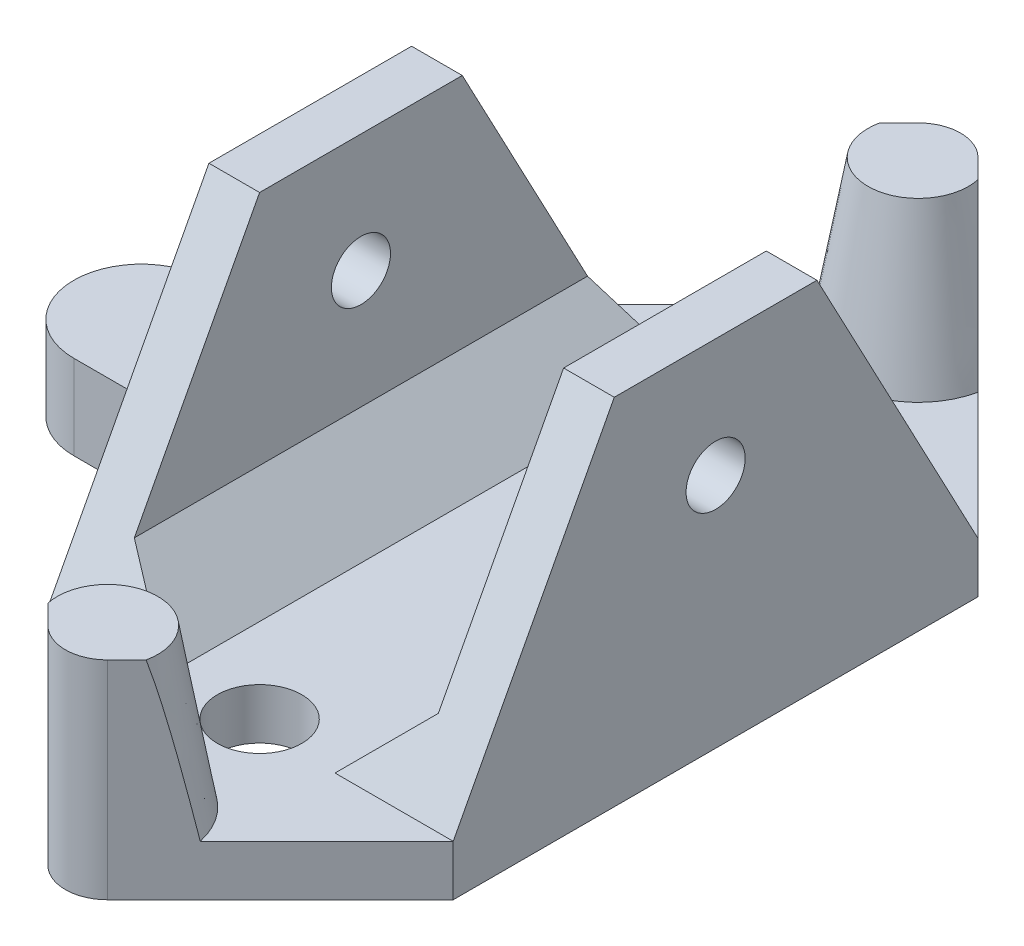
SolidWorks part; units mm, degrees
ref_plane "Plano frontal" through (0, 0, 0) normal (0, 0, 1) x (1, 0, 0)
ref_plane "Plano superior" through (0, 0, 0) normal (0, 1, 0) x (1, 0, 0)
ref_plane "Plano direito" through (0, 0, 0) normal (1, 0, 0) x (0, 0, -1)
sketch "Esboço1" plane through (0, 0, 0) normal (0, 1, 0) x (1, 0, 0)
  line L0 (0, -15) -> (0, 15) construction
  line L1 (-13, -26.5) -> (13, -26.5)
  line L2 (-13, -26.5) -> (-13, -6)
  line L3 (-13, 26.5) -> (13, 26.5)
  line L4 (13, -26.5) -> (13, -6)
  line L5 (-13, -26.5) -> (13, 26.5) construction
  line L6 (-13, 26.5) -> (13, -26.5) construction
  line L7 (0, 24) -> (0, 26.5)
  line L8 (0, 24) -> (-2.5, 24)
  line L9 (0, 24) -> (-2.5, 26.5) construction
  line L10 (0, 24) -> (2.5, 26.5) construction
  line L11 (-1.7678, 25.7678) -> (-13, 14.5355)
  line L12 (1.7678, 25.7678) -> (13, 14.5355)
  line L13 (-7.3839, 0) -> (7.3839, 0) construction
  line L14 (-9, -6) -> (-9, 6)
  line L15 (1.7678, -25.7678) -> (13, -14.5355)
  line L16 (-12, -6) -> (-12, 6)
  line L17 (13, 6) -> (9, 6)
  line L18 (9, -6) -> (9, 6)
  line L19 (-13, 6) -> (-9, 6)
  line L20 (13, -6) -> (9, -6)
  line L21 (-13, -6) -> (-9, -6)
  line L22 (-1.7678, -25.7678) -> (-13, -14.5355)
  line L23 (12, 6) -> (12, -6)
  line L24 (13, 6) -> (13, 26.5)
  line L25 (-13, 6) -> (-13, 26.5)
  circle A0 centre (0, 15) radius 2.5
  circle A1 centre (0, -15) radius 2.5
  circle A2 centre (0, 24) radius 2.5
  circle A3 centre (0, -24) radius 2.5
  point P0 (0, 0)
  point P9 (0, 0)
  point P24 (0, 0)
  point P35 (-9, 0)
  dimension "D4" = 5
  dimension "D5" = 5
  dimension "D6" = 5
  dimension "D1" = 26
  dimension "D2" = 53
  dimension "D3" = 30
  dimension "D7" = 2.5
  dimension "D8" = 12
  dimension "D9" = 4
  dimension "D10" = 3
  dimension "D11" = 3
extrude "Ressalto-extrusão1" add sketch "Esboço1" along normal blind 5 contours L22 A3 L15 L4 L20 L18 L17 L12 A2 L11 L2 L19 L14 L21 A1 A0 region at (0, 0, 0)
extrude "Ressalto-extrusão2" add sketch "Esboço1<3>" along normal blind 12.3 contours A3 | A2 L7 L8 | L7 A2 L8 region at (0, 0, 24) region at (-1.061, 0, -25.061) region at (0.3537, 0, -23.6463)
sketch "Esboço1<3>" plane through (0, 0, 0) normal (0, 1, 0) x (1, 0, 0) same geometry as "Esboço1"
extrude "Ressalto-extrusão3" add sketch "Esboço1<4>" along normal blind 21 contours L20 L4 L17 L18 | L2 L21 L14 L19 region at (-10.5, 0, 0) region at (10.5, 0, 0)
sketch "Esboço1<4>" plane through (0, 0, 0) normal (0, 1, 0) x (1, 0, 0) same geometry as "Esboço1"
sketch "Esboço2" plane through (13, 0, 0) normal (1, 0, 0) x (0, 0, -1)
  line L0 (0, 0) -> (0, 14)
  circle A0 centre (0, 14) radius 1.75
  dimension "D2" = 3.5
  dimension "D1" = 14
extrude "Corte-extrusão1" cut sketch "Esboço2" against normal through all contours A0 region at (13, 12.7976, -1.2024)
ref_plane "Plano1" through (0, 0, 0) normal (1, 0, 0) x (0, 0, -1)
sketch "Esboço12" plane through (-13, 0, 0) normal (-1, 0, 0) x (0, 0, 1)
  line L1 (6, 5) -> (21, 5)
  line L2 (6, 5) -> (6, 0)
  line L3 (6, 0) -> (21, 0)
  line L4 (21, 5) -> (21, 0)
  line L5 (-6, 5) -> (-21, 5)
  line L6 (-6, 5) -> (-6, 0)
  line L7 (-6, 0) -> (-21, 0)
  line L8 (-21, 5) -> (-21, 0)
  dimension "D1" = 15
  dimension "D2" = 15
extrude "Corte-extrusão4" cut sketch "Esboço12" against normal blind 1
mirror "Espelhar2" about plane through (0, 0, 0) normal (1, 0, 0) of "Corte-extrusão4"
sketch "Esboço19" plane through (0, 5, 0) normal (0, 1, 0) x (1, 0, 0)
  line L10 (-9, 6) -> (-9, -6)
  line L11 (12, 6) -> (12, 15.5355)
  line L12 (-12, -15.5355) -> (-1.7678, -25.7678)
  line L13 (1.7678, -25.7678) -> (12, -15.5355)
  line L14 (12, 6) -> (12, 15.5355)
  line L15 (9, -6) -> (9, 6)
  line L16 (-12, 15.5355) -> (-12, 9)
  line L17 (12, 15.5355) -> (1.7678, 25.7678)
  line L18 (-1.7678, 25.7678) -> (-12, 15.5355)
  line L19 (-12, 15.5355) -> (-12, 9)
  line L20 (-9, 6) -> (-9, -6)
  line L21 (-12, 9) -> (-12, 6)
  line L22 (-12, -15.5355) -> (-1.7678, -25.7678)
  line L23 (1.7678, -25.7678) -> (12, -15.5355)
  line L24 (-12, 9) -> (-12, 6)
  line L25 (9, -6) -> (9, 6)
  line L26 (-12, 6) -> (-9, 6)
  line L27 (12, 15.5355) -> (1.7678, 25.7678)
  line L28 (-1.7678, 25.7678) -> (-12, 15.5355)
  line L29 (-12, 6) -> (-9, 6)
  line L36 (-9, -6) -> (-12, -6)
  line L37 (-9, -6) -> (-12, -6)
  line L38 (-12, -6) -> (-12, -9)
  line L39 (-12, -6) -> (-12, -9)
  line L40 (-12, -9) -> (-12, -15.5355)
  line L41 (-12, -9) -> (-12, -15.5355)
  line L42 (12, -15.5355) -> (12, -6)
  line L43 (12, -15.5355) -> (12, -6)
  line L44 (12, -6) -> (9, -6)
  line L45 (12, -6) -> (9, -6)
  line L46 (9, 6) -> (12, 6)
  line L47 (9, 6) -> (12, 6)
  arc A2 (1.7678, -25.7678) -> (-1.7678, -25.7678) centre (0, -24) ccw
  arc A3 (-1.7678, 25.7678) -> (1.7678, 25.7678) centre (0, 24) ccw
  arc A4 (1.7678, -25.7678) -> (-1.7678, -25.7678) centre (0, -24) ccw
  arc A5 (-1.7678, 25.7678) -> (1.7678, 25.7678) centre (0, 24) ccw
  dimension "D1" = 0
extrude "Corte-extrusão5" cut sketch "Esboço19" against normal blind 2
chamfer "Chanfro3" distance 12 angle 10 1 edges at (0, 3, -21.5) first distance on face at (0, 1.5, -24.8839)
chamfer "Chanfro4" distance 12 angle 10 1 edges at (0, 3, 21.5) first distance on face at (0, 1.5, 24.8839)
sketch "Esboço20" plane through (12, 0, 0) normal (1, 0, 0) x (0, 0, -1)
  line L0 (-15.5355, 3) -> (-6, 3)
  line L1 (-6, 3) -> (-6, 21)
  line L2 (-6, 21) -> (-15.5355, 3)
  line L3 (0, 21) -> (0, 14) construction
  line L4 (6, 21) -> (-6, 21) construction
  line L5 (15.5355, 3) -> (6, 3)
  line L6 (6, 3) -> (6, 21)
  line L7 (6, 21) -> (15.5355, 3)
extrude "Ressalto-extrusão4" add sketch "Esboço20" against normal blind 3
mirror "Espelhar3" about plane through (0, 0, 0) normal (1, 0, 0) of "Ressalto-extrusão4"
chamfer "Chanfro6" distance 4 angle 45 2 edges at (9, 3, 0) (-9, 3, 0)
sketch "Esboço21" plane through (0, 0, 0) normal (0, -1, 0) x (-1, 0, 0)
  line L0 (12, 0) -> (26, 0) construction
  line L1 (12, -15.5355) -> (12, 15.5355) construction
  line L2 (26, 4) -> (26, -4)
  line L4 (26, -4) -> (12, -4)
  line L5 (26, -4) -> (26, 4)
  line L6 (26, 4) -> (12, 4)
  line L7 (12, -4) -> (12, 4)
  circle A0 centre (19, 0) radius 0.9
  point P9 (26, 0)
  line M10 (12, -15.5355) -> (12, 15.5355)
  dimension "D2" = 1.8
  dimension "D1" = 14
  dimension "D3" = 8
extrude "Ressalto-extrusão5" add sketch "Esboço21" against normal blind 5 contours L0 L4 L5 A0 M10 | L7 L0 A0 L2 L6 region at (-19, 0, -2.0376) region at (-19, 0, 2.0376)
chamfer "Chanfro7" distance 5 angle 45 2 edges at (-12, 2.5, 4) (-12, 2.5, -4)
fillet "Filete1" radius 4 2 edges at (-26, 2.5, -4) (-26, 2.5, 4)
